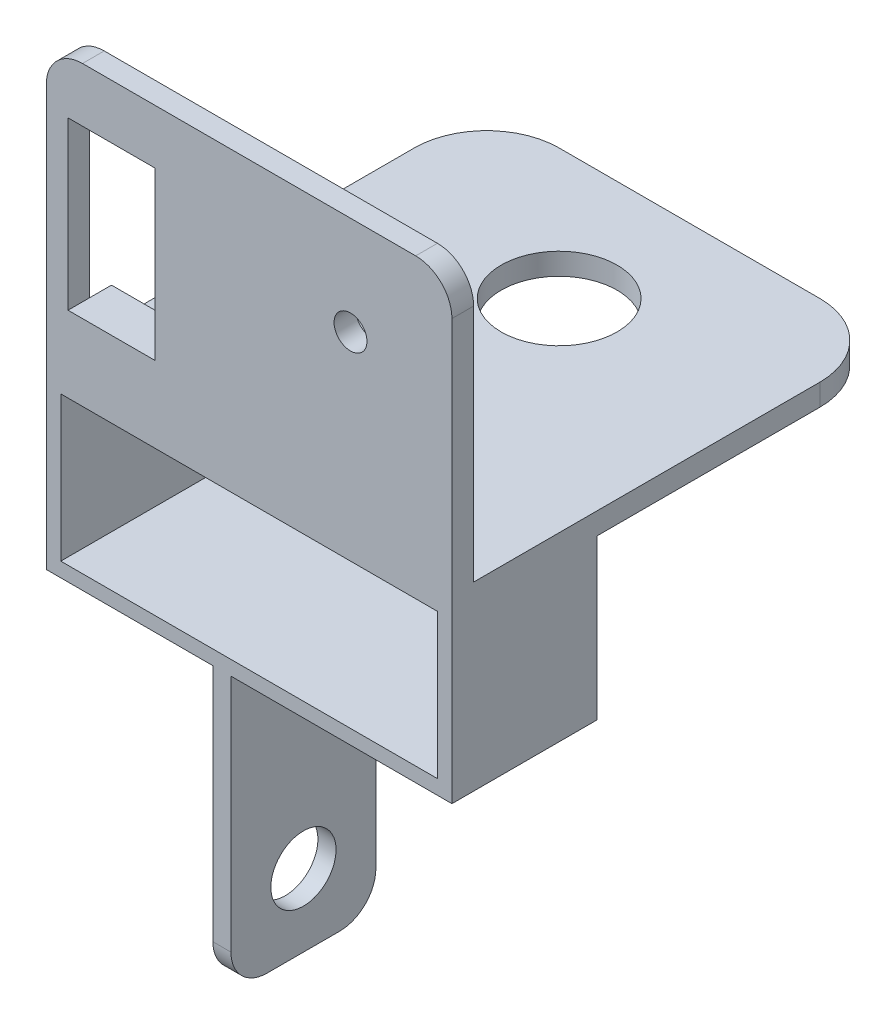
SolidWorks part; units mm, degrees
ref_plane "Front Plane" through (0, 0, 0) normal (0, 0, 1) x (1, 0, 0)
ref_plane "Top Plane" through (0, 0, 0) normal (0, 1, 0) x (1, 0, 0)
ref_plane "Right Plane" through (0, 0, 0) normal (1, 0, 0) x (0, 0, -1)
sketch "Sketch1" plane through (0, 0, 0) normal (0, 1, 0) x (1, 0, 0)
  line L0 (-22.5, -28.5) -> (27.5, -28.5)
  line L2 (-22.5, 29.3) -> (-22.5, -31.5)
  line L3 (-22.5, -31.5) -> (27.5, -31.5)
  line L4 (27.5, 29.3) -> (27.5, -31.5)
  line L6 (-22.5, -31.5) -> (-20.3571, -28.5) construction
  line L7 (-22.5, 4.3) -> (27.5, 4.3)
  line L8 (-22.5, 29.3) -> (27.5, 29.3)
  line L9 (2.5, -31.5) -> (2.5, 29.3) construction
  point P0 (0, 0)
  dimension "D1" = 25
  dimension "D3" = 3
  dimension "D4" = 32.8
  dimension "D6" = 50
extrude "Boss-Extrude1" add sketch "Sketch1" along normal blind 3 contours L7 L2 L0 L4 | L8 L2 L7 L4 region at (2.5, 0, 12.1) region at (2.5, 0, -16.8)
extrude "Boss-Extrude2" add sketch "Sketch1<3>" along normal blind 63 contours L4 L0 L2 L3 region at (2.5, 0, 30)
sketch "Sketch1<3>" plane through (0, 0, 0) normal (0, 1, 0) x (1, 0, 0) same geometry as "Sketch1"
sketch "Sketch7" plane through (0, 0, 0) normal (0, -1, 0) x (1, 0, 0)
  line L0 (2.5, 31.5) -> (2.5, -29.3) construction
  line L1 (-22.5, 31.5) -> (27.5, 31.5) construction
  line L2 (-22.5, -29.3) -> (27.5, -29.3) construction
  line L3 (7.5, 31.5) -> (-2.5, 31.5)
  line L4 (-2.5, 31.5) -> (-2.5, 11.5)
  line L5 (-2.5, 11.5) -> (7.5, 11.5)
  line L6 (7.5, 31.5) -> (7.5, 11.5)
  point P11 (2.5, 11.5)
  dimension "D1" = 20
  dimension "D2" = 5
extrude "Boss-Extrude6" add sketch "Sketch7" along normal blind 60
sketch "Sketch8" plane through (0, 0, 11.5) normal (0, 0, -1) x (-1, 0, 0)
  line L0 (0, -60) -> (0, -40)
  line L2 (0, -40) -> (-7.5, -40)
  line L8 (2.5, 0) -> (-7.5, 0)
  line L9 (-7.5, 0) -> (-7.5, -60)
  line L10 (-7.5, -60) -> (2.5, -60)
  line L11 (2.5, -60) -> (2.5, 0)
  line L12 (2.5, 0) -> (-7.5, 0)
  line L13 (-7.5, 0) -> (-7.5, -60)
  line L14 (-7.5, -60) -> (2.5, -60)
  line L15 (2.5, -60) -> (2.5, 0)
  line M7 (-7.5, 0) -> (-7.5, -60)
  line M8 (-7.5, -60) -> (2.5, -60)
  dimension "D3" = 20
  dimension "D2" = 0
extrude "Cut-Extrude4" cut sketch "Sketch8" against normal blind 60 contours M7 M8 region at (3.75, -50, 11.5)
sketch "Sketch10" plane through (0, 0, 0) normal (1, 0, 0) x (0, 0, -1)
  circle A0 centre (-21.5, -50) radius 4.5
  dimension "D1" = 9
extrude "Cut-Extrude5" cut sketch "Sketch10" against normal blind 60
fillet "Fillet1" radius 5 1 edges at (7.5, -20, 11.5)
fillet "Fillet2" radius 5 1 edges at (7.5, -20, 31.5)
sketch "Sketch11" plane through (0, 0, 31.5) normal (0, 0, 1) x (1, 0, 0)
  line L2 (7.5, -40) -> (0, -40)
  line L3 (7.5, 0) -> (7.5, -40) construction
  line L4 (7.5, -14.5528) -> (7.5, -40)
  line L5 (0, -40) -> (0, -20)
  arc A3 (0, -20) -> (7.5, -14.5528) centre (6.4736, -21.0264) cw
extrude "Cut-Extrude6" cut sketch "Sketch11" against normal up to next
fillet "Fillet4" radius 5 2 edges at (-1.25, -60, 31.5) (-1.25, -60, 11.5)
ref_plane "Plane1" through (27.5, 3, 28.5) normal (0, -1, 0) x (-1, 0, 0)
sketch "Sketch13" plane through (27.5, 0, 0) normal (1, 0, 0) x (0, 0, -1)
  line L6 (-31.5, 0) -> (29.3, 0)
  line L7 (29.3, 0) -> (29.3, 3)
  line L8 (29.3, 3) -> (-28.5, 3)
  line L9 (-28.5, 3) -> (-28.5, 63)
  line L10 (-28.5, 63) -> (-31.5, 63)
  line L11 (-31.5, 63) -> (-31.5, 0)
  line L12 (-31.5, 0) -> (29.3, 0)
  line L13 (29.3, 0) -> (29.3, 3)
  line L14 (29.3, 3) -> (-28.5, 3)
  line L15 (-28.5, 3) -> (-28.5, 63)
  line L16 (-28.5, 63) -> (-31.5, 63)
  line L17 (-31.5, 63) -> (-31.5, 0)
  dimension "D1" = 0
extrude "Boss-Extrude7" add sketch "Sketch13" along normal blind 3
sketch "Sketch14" plane through (-22.5, 0, 0) normal (-1, 0, 0) x (0, 0, 1)
  line L6 (-29.3, 0) -> (31.5, 0)
  line L7 (31.5, 0) -> (31.5, 63)
  line L8 (31.5, 63) -> (28.5, 63)
  line L9 (28.5, 63) -> (28.5, 3)
  line L10 (28.5, 3) -> (-29.3, 3)
  line L11 (-29.3, 3) -> (-29.3, 0)
  line L12 (-29.3, 0) -> (31.5, 0)
  line L13 (31.5, 0) -> (31.5, 63)
  line L14 (31.5, 63) -> (28.5, 63)
  line L15 (28.5, 63) -> (28.5, 3)
  line L16 (28.5, 3) -> (-29.3, 3)
  line L17 (-29.3, 3) -> (-29.3, 0)
  dimension "D1" = 0
extrude "Boss-Extrude8" add sketch "Sketch14" along normal blind 3
sketch "Sketch15" plane through (0, 3, 0) normal (0, 1, 0) x (1, 0, 0)
  line L0 (2.5, 29.3) -> (2.5, -28.5) construction
  line L1 (-25.5, 29.3) -> (30.5, 29.3) construction
  line L2 (-25.5, -28.5) -> (30.5, -28.5) construction
  circle A0 centre (2.5, 11.3) radius 8
  circle A1 centre (2.5, -14.7) radius 8
  dimension "D1" = 16
  dimension "D2" = 16
  dimension "D3" = 26
  dimension "D4" = 18
extrude "Cut-Extrude7" cut sketch "Sketch15" against normal blind 3
sketch "Sketch16" plane through (0, 0, 0) normal (1, 0, 0) x (0, 0, -1)
  line L0 (-31.5, -20) -> (-11.5, -20)
  line L1 (-11.5, -20) -> (-11.5, 0)
  line L2 (-11.5, 0) -> (-31.5, 0.262)
  line L3 (-31.5, 0.262) -> (-31.5, -20)
extrude "Cut-Extrude8" cut sketch "Sketch16" against normal mid plane 80
sketch "Sketch17" plane through (-2.5, 0, 0) normal (-1, 0, 0) x (0, 0, 1)
  line L0 (11.5, -22) -> (31.5, -22)
  line L1 (11.5, -55) -> (11.5, -20) construction
  line L2 (31.5, -55) -> (31.5, -20) construction
  line L3 (31.5, -20) -> (11.5, -20) construction
  line L8 (31.5, -55) -> (31.5, -20)
  line L9 (31.5, -20) -> (11.5, -20)
  line L10 (11.5, -20) -> (11.5, -55)
  line L11 (16.5, -60) -> (26.5, -60)
  line L12 (31.5, -55) -> (31.5, -20)
  line L13 (31.5, -20) -> (11.5, -20)
  line L14 (11.5, -20) -> (11.5, -55)
  line L15 (16.5, -60) -> (26.5, -60)
  arc A2 (11.5, -55) -> (16.5, -60) centre (16.5, -55) ccw
  arc A3 (26.5, -60) -> (31.5, -55) centre (26.5, -55) ccw
  arc A4 (11.5, -55) -> (16.5, -60) centre (16.5, -55) ccw
  arc A5 (26.5, -60) -> (31.5, -55) centre (26.5, -55) ccw
  line M9 (31.5, -55) -> (31.5, -20)
  line M10 (31.5, -20) -> (11.5, -20)
  line M11 (11.5, -20) -> (11.5, -55)
  dimension "D1" = 2
  dimension "D2" = 0
extrude "Boss-Extrude9" add sketch "Sketch17" along normal blind 23 and the other way blind 33 contours L0 M11 M9 M10 region at (-2.5, -21, 21.5)
sketch "Sketch19" plane through (0, -20, 0) normal (0, 1, 0) x (1, 0, 0)
  line L0 (28.5, -11.5) -> (28.5, -31.5)
  line L1 (-25.5, -11.5) -> (30.5, -11.5) construction
  line L2 (-25.5, -31.5) -> (30.5, -31.5) construction
  line L3 (30.5, -31.5) -> (30.5, -11.5) construction
  line L8 (-25.5, -31.5) -> (30.5, -31.5)
  line L9 (30.5, -31.5) -> (30.5, -11.5)
  line L10 (30.5, -11.5) -> (-25.5, -11.5)
  line L11 (-25.5, -11.5) -> (-25.5, -31.5)
  line L12 (-25.5, -31.5) -> (30.5, -31.5)
  line L13 (30.5, -31.5) -> (30.5, -11.5)
  line L14 (30.5, -11.5) -> (-25.5, -11.5)
  line L15 (-25.5, -11.5) -> (-25.5, -31.5)
  line M6 (-25.5, -31.5) -> (30.5, -31.5)
  line M7 (30.5, -31.5) -> (30.5, -11.5)
  line M8 (30.5, -11.5) -> (-25.5, -11.5)
  line M9 (-25.5, -11.5) -> (-25.5, -31.5)
  dimension "D1" = 2
  dimension "D2" = 0
extrude "Boss-Extrude25" add sketch "Sketch19" along normal up to surface (20.262 mm away) contours L0 M8 M9 M6 | L0 M8 M6 M7 region at (29.5, -20, 21.5) region at (1.5, -20, 21.5) up to face at (2.5, 0.1118, 20.0333)
sketch "Sketch25" plane through (0, 0, 11.5) normal (0, 0, -1) x (-1, 0, 0)
  line L0 (-28.5, 0) -> (-28.5, -20)
  line L1 (25.5, 0) -> (-30.5, 0) construction
  line L2 (-28.5, -20) -> (23.5, -20)
  line L3 (23.5, -20) -> (23.5, 0)
  line L4 (23.5, 0) -> (-28.5, 0)
  line L5 (-30.5, 0) -> (-30.5, -22) construction
  line L6 (25.5, 0) -> (25.5, -22) construction
  line L7 (2.5, -22) -> (25.5, -22) construction
  line L18 (-9.8321, 0) -> (-30.5, 0)
  line L19 (-30.5, 0) -> (-30.5, -22)
  line L20 (-30.5, -22) -> (0, -22)
  line L21 (0, -22) -> (0, -55)
  line L22 (0, -55) -> (2.5, -55)
  line L23 (2.5, -55) -> (2.5, -22)
  line L24 (2.5, -22) -> (25.5, -22)
  line L25 (25.5, -22) -> (25.5, 0)
  line L26 (25.5, 0) -> (4.8321, 0)
  line L27 (4.8321, 0) -> (-9.8321, 0)
  line L28 (-9.8321, 0) -> (-30.5, 0)
  line L29 (-30.5, 0) -> (-30.5, -22)
  line L30 (-30.5, -22) -> (0, -22)
  line L31 (0, -22) -> (0, -55)
  line L32 (0, -55) -> (2.5, -55)
  line L33 (2.5, -55) -> (2.5, -22)
  line L34 (2.5, -22) -> (25.5, -22)
  line L35 (25.5, -22) -> (25.5, 0)
  line L36 (25.5, 0) -> (4.8321, 0)
  line L37 (4.8321, 0) -> (-9.8321, 0)
  line M14 (-9.8321, 0) -> (-30.5, 0)
  line M22 (25.5, 0) -> (4.8321, 0)
  line M23 (4.8321, 0) -> (-9.8321, 0)
  dimension "D1" = 2
  dimension "D2" = 2
  dimension "D3" = 2
  dimension "D4" = 0
extrude "Cut-Extrude9" cut sketch "Sketch25" against normal up to next contours L2 L3 L0 M22 M23 M14 region at (2.5, -10, 11.5)
sketch "Sketch27" plane through (0, 0, 0) normal (0, -1, 0) x (1, 0, 0)
  circle A0 centre (2.5, 14.7) radius 8
  dimension "D1" = 16
extrude "Cut-Extrude10" cut sketch "Sketch27" against normal up to next
sketch "Sketch28" plane through (0, 0, 28.5) normal (0, 0, -1) x (-1, 0, 0)
  line L0 (-2.5, 3) -> (-2.5, 63) construction
  line L1 (25.5, 3) -> (-30.5, 3) construction
  line L2 (25.5, 63) -> (-30.5, 63) construction
  line L3 (5.5, 63) -> (5.5, 3)
  line L4 (25.5, 3) -> (-30.5, 3) construction
  line L5 (10.5, 38) -> (10.5, 6)
  line L6 (10.5, 6) -> (22.5, 6)
  line L7 (22.5, 6) -> (22.5, 38)
  line L8 (22.5, 38) -> (10.5, 38)
  line L9 (25.5, 63) -> (25.5, 3) construction
  line L10 (10.5, 33.5) -> (22.5, 33.5)
  line L11 (10.5, 10.5) -> (22.5, 10.5)
  point P20 (16.5, 33.5)
  dimension "D1" = 8
  dimension "D2" = 12
  dimension "D3" = 3
  dimension "D4" = 3
  dimension "D5" = 32
  dimension "D6" = 4.5
  dimension "D7" = 4.5
extrude "Boss-Extrude26" add sketch "Sketch28" along normal blind 3 contours L5 L10 L7 L8 | L11 L5 L6 L7 region at (-16.5, 35.75, 28.5) region at (-16.5, 8.25, 28.5)
extrude "Cut-Extrude11" cut sketch "Sketch28<3>" against normal blind 3 contours L5 L11 L7 L10 region at (-16.5, 22, 28.5)
sketch "Sketch28<3>" plane through (0, 0, 28.5) normal (0, 0, -1) x (-1, 0, 0) same geometry as "Sketch28"
sketch "Sketch29" plane through (0, 0, 28.5) normal (0, 0, -1) x (-1, 0, 0)
  line L0 (25.5, 41) -> (-30.5, 41)
  line L1 (25.5, 63) -> (25.5, 3) construction
  line L2 (-30.5, 3) -> (-30.5, 63) construction
  line L3 (22.5, 38) -> (10.5, 38) construction
  line L7 (-30.5, 3) -> (25.5, 3)
  line L8 (25.5, 3) -> (25.5, 63)
  line L9 (25.5, 63) -> (-30.5, 63)
  line L10 (-30.5, 63) -> (-30.5, 3)
  line L11 (-30.5, 3) -> (25.5, 3)
  line L12 (25.5, 3) -> (25.5, 63)
  line L13 (25.5, 63) -> (-30.5, 63)
  line L14 (-30.5, 63) -> (-30.5, 3)
  line M15 (25.5, 3) -> (25.5, 63)
  line M16 (25.5, 63) -> (-30.5, 63)
  line M17 (-30.5, 63) -> (-30.5, 3)
  dimension "D2" = 3
  dimension "D1" = 0
extrude "Cut-Extrude12" cut sketch "Sketch29" against normal blind 3 contours L0 M15 M16 M17 region at (2.5, 52, 28.5)
fillet "Fillet5" radius 5 2 edges at (30.5, 41, 30) (-25.5, 41, 30)
fillet "Fillet6" radius 10 2 edges at (30.5, 1.5, -29.3) (-25.5, 1.5, -29.3)
sketch "Sketch30" plane through (0, 0, 28.5) normal (0, 0, -1) x (-1, 0, 0)
  line L0 (-2.5, 41) -> (-2.5, 3) construction
  line L1 (20.5, 41) -> (-25.5, 41) construction
  line L2 (25.5, 3) -> (-30.5, 3) construction
  circle A0 centre (-16.5, 27.4) radius 2.2712
  dimension "D1" = 13.6
  dimension "D2" = 14
extrude "Cut-Extrude13" cut sketch "Sketch30" against normal up to next
